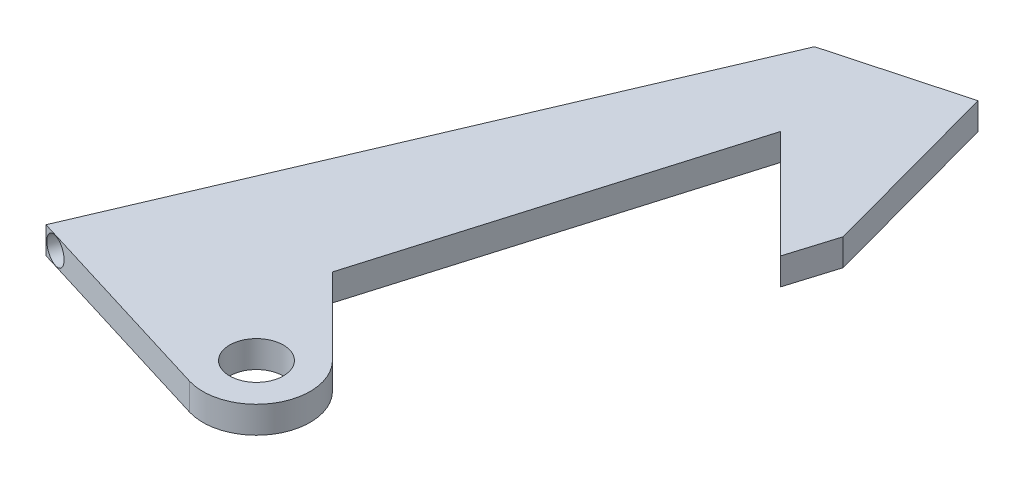
SolidWorks part; units mm, degrees
ref_plane "Front Plane" through (0, 0, 0) normal (0, 0, 1) x (1, 0, 0)
ref_plane "Top Plane" through (0, 0, 0) normal (0, 1, 0) x (1, 0, 0)
ref_plane "Right Plane" through (0, 0, 0) normal (1, 0, 0) x (0, 0, -1)
sketch "Sketch1" plane through (0, 0, 0) normal (0, 1, 0) x (1, 0, 0)
  line L4 (16.4831, 10.0385) -> (1.9444, 24.5773)
  line L5 (1.9444, 24.5773) -> (-6.9385, -5.4107)
  line L6 (23.67, 13.942) -> (15.9928, 42.1674)
  line L7 (15.9928, 42.1674) -> (14.7311, 46.8062)
  line L8 (14.7311, 46.8062) -> (-8.0699, 40.6045)
  line L9 (-8.0699, 40.6045) -> (-48.8995, -54.9336)
  line L11 (16.4831, 10.0385) -> (21.0706, 5.4511)
  line L12 (21.0706, 5.4511) -> (23.67, 13.942)
  line L13 (-6.9385, -5.4107) -> (-16.2313, -36.7829)
  line L14 (-2.4976, -50.5193) -> (-16.2313, -36.7829)
  line L15 (-0.2503, -64.2218) -> (8.9811, -34.0664) construction
  line L16 (-33.45, -172.6721) -> (154.2855, 440.5857) construction
  line L17 (-1.4647, -63.85) -> (7.7667, -33.6946) construction
  line L18 (-10.7741, -61.0002) -> (-1.5427, -30.8448) construction
  line L19 (-48.8995, -54.9336) -> (-12.1637, -66.2238)
  circle A4 centre (-9.3655, -57.1191) radius 4.7625
  arc A5 (-12.1637, -66.2238) -> (-2.4976, -50.5193) centre (-9.3655, -57.1191) ccw
  dimension "D1" = 1.27
extrude "Boss-Extrude1" add sketch "Sketch1" along normal blind 4.7625
sketch "Sketch2" plane through (-19.6462, 0, 63.9242) normal (-0.2938, 0, 0.9559) x (0.9559, 0, 0.2938)
  line L0 (-30.6038, 2.3813) -> (-28.0638, 2.3813) construction
  line L1 (-30.6038, 4.7625) -> (-30.6038, 0) construction
hole_wizard "#14 (0.182) Diameter Hole1" positions "Sketch3" profile "Sketch4" hole size "#14" standard "ANSI Inch"
sketch "Sketch3" plane through (-19.6462, 0, 63.9242) normal (-0.2938, 0, 0.9559) x (0.9559, 0, 0.2938)
  point P0 (-28.0638, 2.3813)
sketch "Sketch4" plane through (-46.4716, 2.3813, 55.6798) normal (0, 1, 0) x (0.9559, 0, 0.2938)
  line L0 (0, 0) -> (0, 3.9288)
  line L1 (0, 3.9288) -> (2.3114, 2.54)
  line L2 (2.3114, 2.54) -> (2.3114, 0)
  line L5 (2.3114, 0) -> (0, 0)
  line L10 (0, 3.9288) -> (-2.3114, 2.54) construction
  line L11 (0, -6.35) -> (0, 107.95) construction
  dimension "Hole Dia." = 4.6228
  dimension "Hole Depth" = 2.54
  dimension "Drill Angle" = 118
